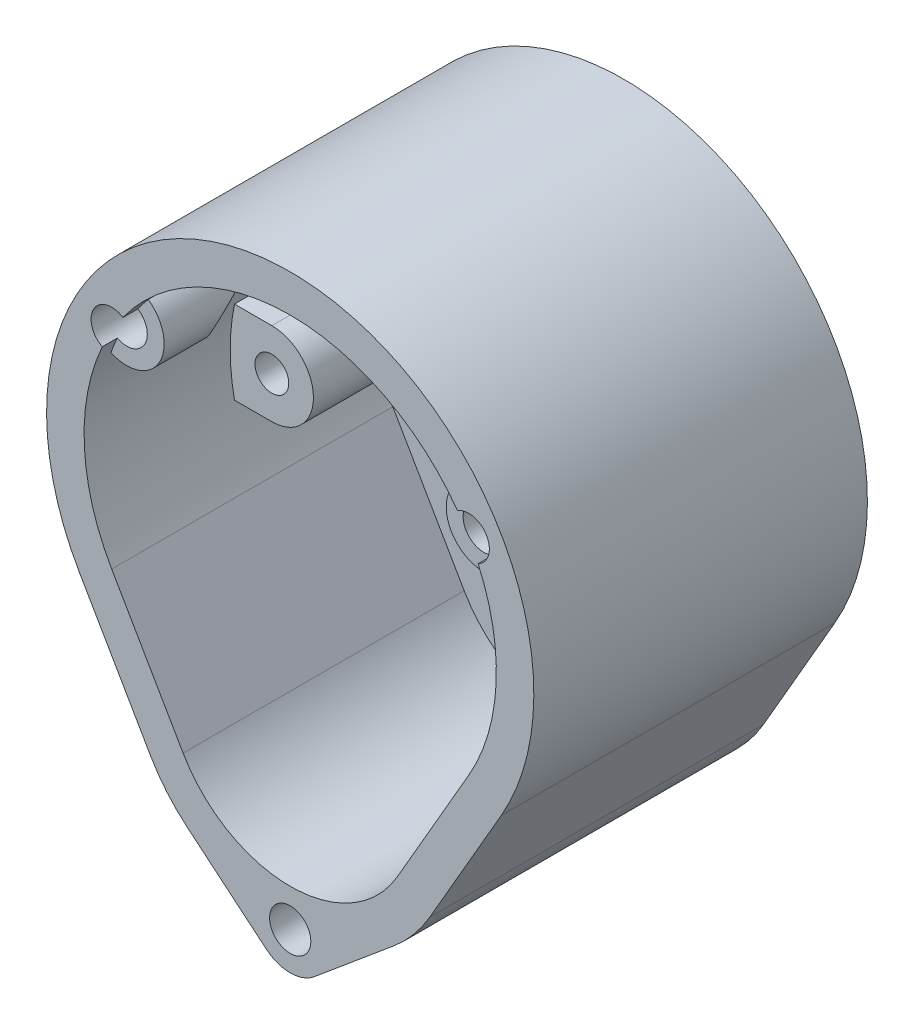
SolidWorks part; units mm, degrees
material "PET"
ref_plane "Front Plane" through (0, 0, 0) normal (0, 0, 1) x (1, 0, 0)
ref_plane "Top Plane" through (0, 0, 0) normal (0, 1, 0) x (1, 0, 0)
ref_plane "Right Plane" through (0, 0, 0) normal (1, 0, 0) x (0, 0, -1)
sketch "Sketch1" plane through (0, 0, 0) normal (0, 0, 1) x (1, 0, 0)
  line L0 (-28.1458, -16.25) -> (-18.6195, -32.75)
  line L1 (28.1458, -16.25) -> (18.6195, -32.75)
  line L2 (0, 0) -> (0, -22) construction
  arc A0 (28.1458, -16.25) -> (-28.1458, -16.25) centre (0, 0) ccw
  arc A1 (-18.6195, -32.75) -> (18.6195, -32.75) centre (0, -22) ccw
  dimension "D1" = 65
  dimension "D2" = 22
  dimension "D3" = 43
extrude "Boss-Extrude1" add sketch "Sketch1" along normal blind 7
sketch "Sketch2" plane through (0, 0, 7) normal (0, 0, 1) x (1, 0, 0)
  line L0 (0, 0) -> (0, -22) construction
  circle A0 centre (0, -22) radius 2.75
  dimension "D1" = 22
  dimension "D2" = 5.5
extrude "Cut-Extrude1" cut sketch "Sketch2" against normal through all
sketch "Sketch3" plane through (0, 0, 7) normal (0, 0, 1) x (1, 0, 0)
  circle A0 centre (0, -22) radius 7.1
  dimension "D1" = 14.2
extrude "Cut-Extrude2" cut sketch "Sketch3" against normal blind 5
sketch "Sketch4" plane through (0, 0, 7) normal (0, 0, 1) x (1, 0, 0)
  line L0 (-28.1458, -16.25) -> (-18.6195, -32.75)
  line L1 (28.1458, -16.25) -> (18.6195, -32.75)
  line L2 (-23.8157, -13.75) -> (-14.2894, -30.25)
  line L3 (23.8157, -13.75) -> (14.2894, -30.25)
  arc A0 (28.1458, -16.25) -> (-28.1458, -16.25) centre (0, 0) ccw
  arc A1 (-18.6195, -32.75) -> (18.6195, -32.75) centre (0, -22) ccw
  arc A2 (28.1458, -16.25) -> (-28.1458, -16.25) centre (0, 0) ccw construction
  arc A3 (-18.6195, -32.75) -> (18.6195, -32.75) centre (0, -22) ccw construction
  arc A4 (23.8157, -13.75) -> (-23.8157, -13.75) centre (0, 0) ccw
  arc A5 (-14.2894, -30.25) -> (14.2894, -30.25) centre (0, -22) ccw
  dimension "D1" = 5
extrude "Boss-Extrude2" add sketch "Sketch4" along normal blind 37.5
sketch "Sketch5" plane through (0, 0, 7) normal (0, 0, 1) x (1, 0, 0)
  line L0 (-21.95, 0) -> (21.95, 0) construction
  line L1 (-21.95, 5.55) -> (-26.9341, 5.55)
  line L2 (-21.95, -5.55) -> (-26.9341, -5.55)
  line L3 (21.95, 5.55) -> (26.9341, 5.55)
  line L4 (21.95, -5.55) -> (26.9341, -5.55)
  circle A0 centre (-21.95, 0) radius 2.25
  circle A1 centre (21.95, 0) radius 2.25
  arc A2 (-21.95, -5.55) -> (-21.95, 5.55) centre (-21.95, 0) ccw
  arc A3 (21.95, 5.55) -> (21.95, -5.55) centre (21.95, 0) ccw
  arc A4 (-26.9341, 5.55) -> (-26.9341, -5.55) centre (0, 0) ccw
  arc A5 (23.8157, -13.75) -> (-23.8157, -13.75) centre (0, 0) ccw construction
  arc A6 (26.9341, -5.55) -> (26.9341, 5.55) centre (0, 0) ccw
  dimension "D1" = 4.5
  dimension "D2" = 4.5
  dimension "D3" = 43.9
extrude "Boss-Extrude3" add sketch "Sketch5" along normal blind 18
sketch "Sketch6" plane through (0, 0, 7) normal (0, 0, 1) x (1, 0, 0)
  line L0 (-12, 15.95) -> (-12, -1.05) construction
  line L1 (-12, -1.05) -> (12, -1.05) construction
  line L2 (-12, 15.95) -> (12, 15.95) construction
  circle A0 centre (-12, 15.95) radius 1.6
  circle A1 centre (12, 15.95) radius 1.6
  circle A2 centre (-12, -1.05) radius 1.6
  circle A3 centre (12, -1.05) radius 1.6
  dimension "D1" = 3.2
  dimension "D2" = 3.2
  dimension "D3" = 3.2
  dimension "D4" = 3.2
  dimension "D6" = 15.95
  dimension "D5" = 12
  dimension "D7" = 24
  dimension "D8" = 24
  dimension "D9" = 17
extrude "Cut-Extrude3" cut sketch "Sketch6" against normal up to next
sketch "Sketch7" plane through (0, 0, 44.5) normal (0, 0, 1) x (1, 0, 0)
  line L0 (-13.784, -38.5) -> (-3.2056, -47.3372)
  line L1 (0, 0) -> (0, -43.5) construction
  line L2 (0, 0) -> (23.8157, 13.75) construction
  line L3 (0, 0) -> (-23.8157, 13.75) construction
  line L4 (13.784, -38.5) -> (3.2056, -47.3372)
  circle A1 centre (-23.8157, 13.75) radius 5
  arc A2 (26.9341, 5.55) -> (-26.9341, 5.55) centre (0, 0) ccw construction
  circle A3 centre (23.8157, 13.75) radius 5
  arc A4 (23.8157, -13.75) -> (-23.8157, -13.75) centre (0, 0) ccw construction
  arc A5 (-3.2056, -47.3372) -> (3.2056, -47.3372) centre (0, -43.5) ccw
  arc A6 (-18.6195, -32.75) -> (18.6195, -32.75) centre (0, -22) ccw construction
  arc A7 (28.1458, -16.25) -> (-28.1458, -16.25) centre (0, 0) ccw construction
  arc A8 (-14.2894, -30.25) -> (14.2894, -30.25) centre (0, -22) ccw construction
  arc A9 (-13.784, -38.5) -> (13.784, -38.5) centre (0, -21.75) ccw
  dimension "D1" = 120
  dimension "D2" = 120
extrude "Boss-Extrude4" add sketch "Sketch7" against normal blind 17.5
sketch "Sketch8" plane through (0, 0, 0) normal (1, 0, 0) x (0, 0, -1)
  line L0 (-27, -43.5) -> (-35.6603, -48.5)
  line L1 (-44.5, -48.5) -> (-27, -48.5) construction
  line L2 (-35.6603, -48.5) -> (-27, -48.5)
  line L3 (-27, -48.5) -> (-27, -47.3372) construction
  line L4 (-27, -48.5) -> (-27, -43.5)
  line L5 (0, -22) -> (-44.5, -22) construction
  line L6 (0, -32.75) -> (0, -16.25) construction
  line L7 (-44.5, -32.75) -> (-44.5, -16.25) construction
  dimension "D1" = 30
  dimension "D2" = 22
revolve "Cut-Revolve1" cut sketch "Sketch8" angle 90 mid plane about L5
sketch "Sketch9" plane through (0, 0, 0) normal (1, 0, 0) x (0, 0, -1)
  line L0 (-27, 27.5) -> (-35.6603, 22.5)
  line L1 (-35.6603, 22.5) -> (-27, 22.5)
  line L2 (-27, 22.5) -> (-27, 27.5)
  line L3 (0, 32.5) -> (-44.5, 32.5) construction
  line L4 (-44.5, 32.5) -> (-44.5, -16.25) construction
  line L5 (0, 0) -> (-44.5, 0) construction
  dimension "D1" = 5
  dimension "D2" = 5
  dimension "D3" = 30
  dimension "D4" = 17.5
revolve "Cut-Revolve2" cut sketch "Sketch9" angle 145 mid plane about L5
sketch "Sketch10" plane through (0, 0, 44.5) normal (0, 0, 1) x (1, 0, 0)
  line L0 (-23.8157, -13.75) -> (-14.2894, -30.25)
  line L1 (23.8157, -13.75) -> (14.2894, -30.25)
  arc A0 (23.8157, -13.75) -> (-23.8157, -13.75) centre (0, 0) ccw
  arc A1 (-14.2894, -30.25) -> (14.2894, -30.25) centre (0, -22) ccw
extrude "Cut-Extrude4" cut sketch "Sketch10" against normal blind 2
sketch "Sketch11" plane through (0, 0, 44.5) normal (0, 0, 1) x (1, 0, 0)
  circle A0 centre (-23.8157, 13.75) radius 2.75
  arc A1 (-20.9324, 17.8349) -> (-25.9117, 9.2105) centre (0, 0) ccw construction
  circle A2 centre (23.8157, 13.75) radius 2.75
  arc A3 (25.9117, 9.2105) -> (20.9324, 17.8349) centre (0, 0) ccw construction
  circle A4 centre (0, -43.5) radius 2.75
  dimension "D1" = 5.5
  dimension "D2" = 5.5
  dimension "D3" = 5.5
extrude "Cut-Extrude6" cut sketch "Sketch11" against normal blind 12
sketch "Sketch12" plane through (0, 0, 0) normal (0, 0, -1) x (-1, 0, 0)
  line L0 (4.2, -33.55) -> (-5.3, -33.55) construction
  circle A0 centre (4.2, -33.55) radius 1.5
  circle A1 centre (0, -22) radius 2.75 construction
  circle A2 centre (-5.3, -33.55) radius 1.5
  dimension "D2" = 11.55
  dimension "D3" = 3
  dimension "D5" = 3
  dimension "D1" = 4.2
  dimension "D4" = 9.5
extrude "Cut-Extrude7" cut sketch "Sketch12" against normal up to next
chamfer "Chamfer1" distance 2 angle 45 4 edges at (13.6, 15.95, 7) (13.6, -1.05, 7) (-10.4, -1.05, 7) (-10.4, 15.95, 7)
